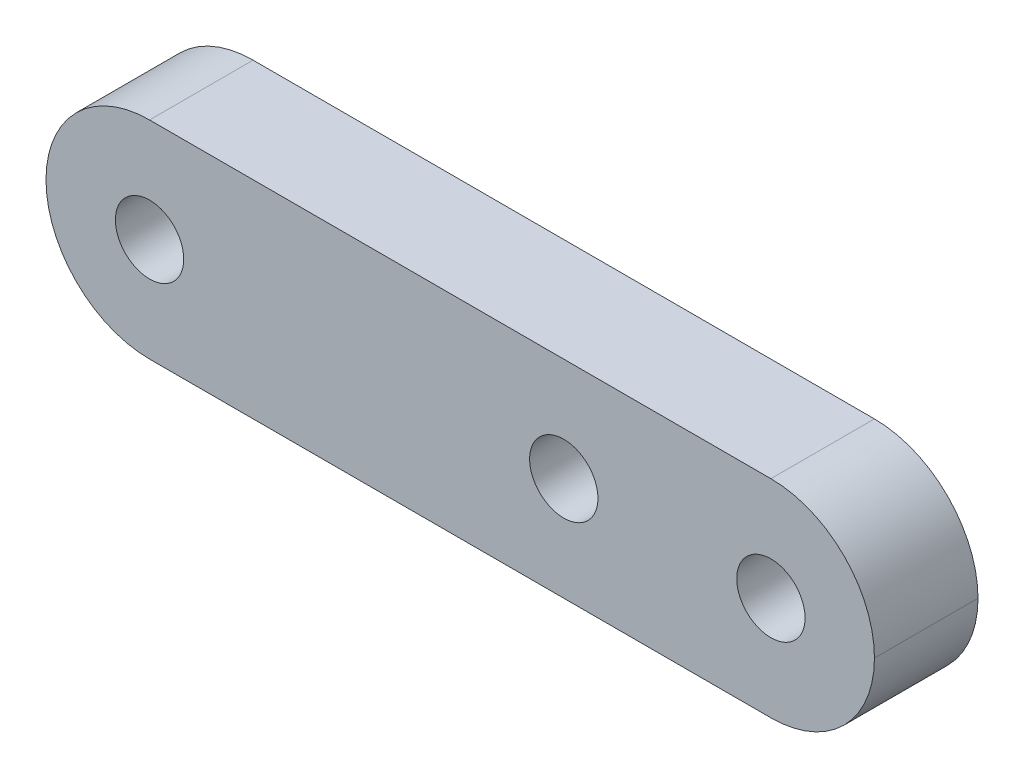
SolidWorks part; units mm, degrees
ref_plane "Přední rovina" through (0, 0, 0) normal (0, 0, 1) x (1, 0, 0)
ref_plane "Horní rovina" through (0, 0, 0) normal (0, 1, 0) x (1, 0, 0)
ref_plane "Pravá rovina" through (0, 0, 0) normal (1, 0, 0) x (0, 0, -1)
sketch "Skica1" plane through (0, 0, 0) normal (0, 0, 1) x (1, 0, 0)
  line L1 (0, 0) -> (40, 0)
  line L2 (0, 0) -> (0, 10)
  line L3 (0, 10) -> (40, 10)
  line L4 (40, 0) -> (40, 10)
  dimension "D1" = 40
  dimension "D2" = 10
extrude "Přidat vysunutím1" add sketch "Skica1" along normal blind 5
sketch "Skica2" plane through (0, 0, 5) normal (0, 0, 1) x (1, 0, 0)
  line L0 (0, 0) -> (40, 0) construction
  line L1 (0, 10) -> (0, 0) construction
  line L2 (40, 0) -> (40, 10) construction
  circle A0 centre (5, 5) radius 1.65
  circle A1 centre (35, 5) radius 1.65
  dimension "D1" = 3.3
  dimension "D2" = 3.3
  dimension "D3" = 5
  dimension "D4" = 5
  dimension "D5" = 5
  dimension "D6" = 5
extrude "Odebrat vysunutím1" cut sketch "Skica2" against normal blind 5
fillet "Zaoblit2" radius 5 4 edges at (40, 0, 2.5) (40, 10, 2.5) (0, 0, 2.5) (0, 10, 2.5)
sketch "Skica3" plane through (0, 0, 5) normal (0, 0, 1) x (1, 0, 0)
  line L0 (5, 0) -> (35, 0) construction
  circle A0 centre (25, 5) radius 1.65
  dimension "D1" = 3.3
  dimension "D2" = 5
  dimension "D3" = 15
extrude "Odebrat vysunutím2" cut sketch "Skica3" against normal blind 10
